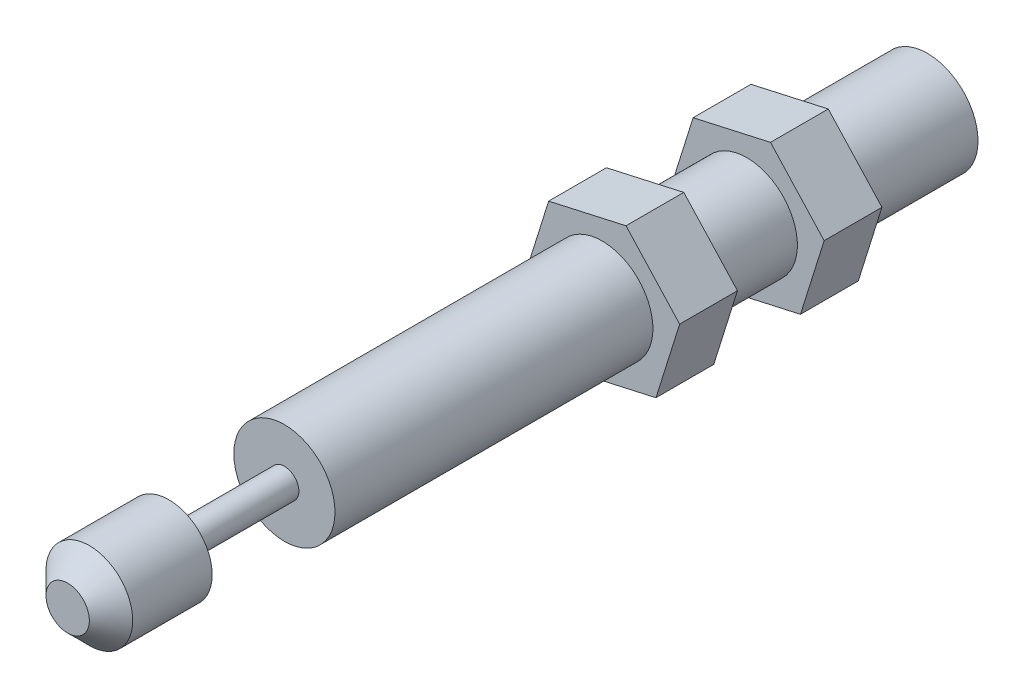
SolidWorks part; units mm, degrees
ref_plane "前视基准面" through (0, 0, 0) normal (0, 0, 1) x (1, 0, 0)
ref_plane "上视基准面" through (0, 0, 0) normal (0, 1, 0) x (1, 0, 0)
ref_plane "右视基准面" through (0, 0, 0) normal (1, 0, 0) x (0, 0, -1)
sketch "草图1" plane through (0, 0, 0) normal (0, 0, 1) x (1, 0, 0)
  circle A0 centre (0, 0) radius 7
  dimension "D1" = 14
extrude "凸台-拉伸1" add sketch "草图1" along normal blind 89
sketch "草图2" plane through (0, 0, 89) normal (0, 0, 1) x (1, 0, 0)
  circle A0 centre (0, 0) radius 2
  dimension "D1" = 4
extrude "凸台-拉伸2" add sketch "草图2" along normal blind 16
sketch "草图3" plane through (0, 0, 105) normal (0, 0, 1) x (1, 0, 0)
  circle A0 centre (0, 0) radius 6
  dimension "D1" = 12
extrude "凸台-拉伸3" add sketch "草图3" along normal blind 14
chamfer "倒角1" distance 3 angle 45 1 edges at (6, 0, 119)
ref_plane "基准面1" through (0, 0, 25) normal (0, 0, -1) x (-1, 0, 0)
sketch "草图4" plane through (0, 0, 25) normal (0, 0, -1) x (-1, 0, 0)
  line L1 (-3.2778, 10.4685) -> (-10.7049, 2.3956)
  line L2 (-10.7049, 2.3956) -> (-7.4271, -8.0729)
  line L3 (-7.4271, -8.0729) -> (3.2778, -10.4685)
  line L4 (3.2778, -10.4685) -> (10.7049, -2.3956)
  line L5 (10.7049, -2.3956) -> (7.4271, 8.0729)
  line L6 (7.4271, 8.0729) -> (-3.2778, 10.4685)
  circle A0 centre (0, 0) radius 9.5 construction
  dimension "D1" = 19
extrude "凸台-拉伸4" add sketch "草图4" along normal blind 8
ref_axis "基准轴1" through (0, 0, 89) along (0, 0, -1)
pattern_linear "阵列(线性)1" count 2 spacing 20 along (0, 0, 1) of "凸台-拉伸4"
